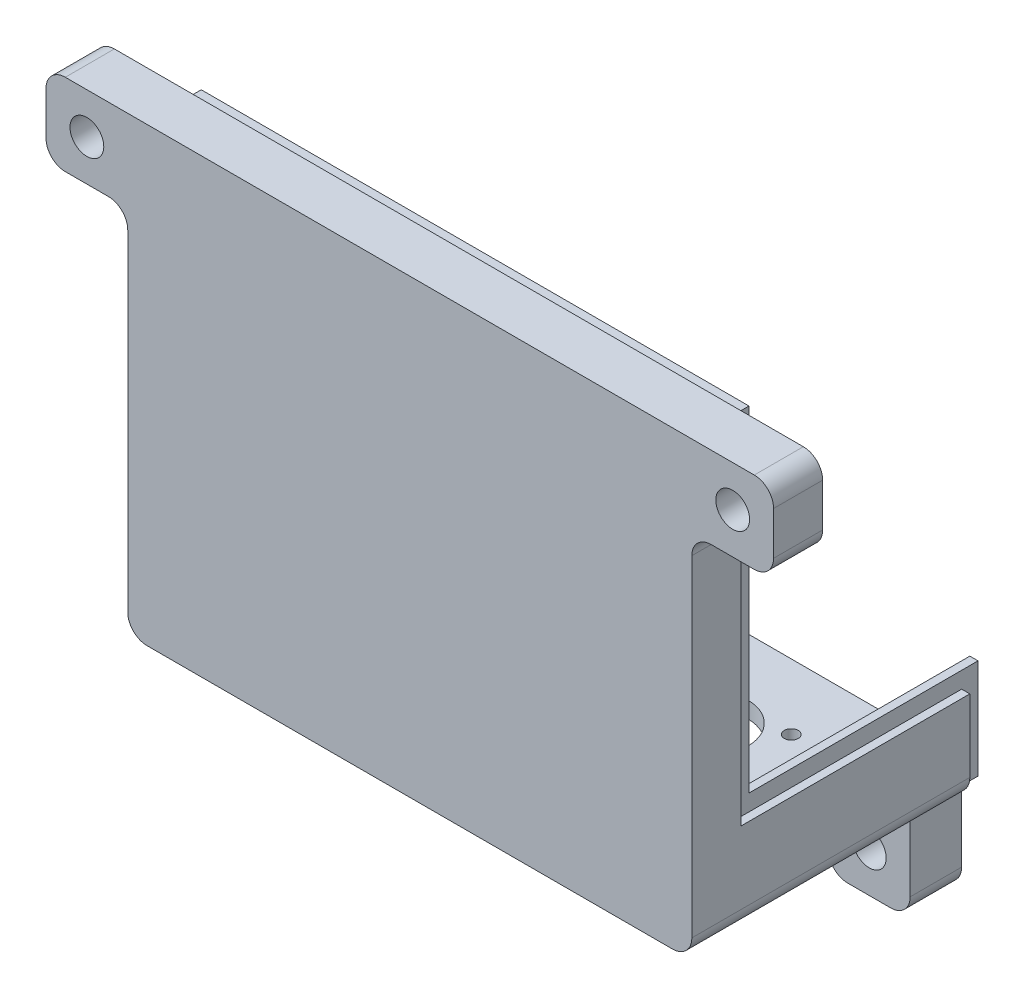
SolidWorks part; units mm, degrees
material "ABS"
ref_plane "X-Y Datum" through (0, 0, 0) normal (0, 0, 1) x (1, 0, 0)
ref_plane "X-Z Datum" through (0, 0, 0) normal (0, 1, 0) x (1, 0, 0)
ref_plane "Y-Z Datum" through (0, 0, 0) normal (1, 0, 0) x (0, 0, -1)
sketch "Sketch1" plane through (0, 0, 0) normal (0, 0, 1) x (1, 0, 0)
  line L0 (6.33, 73.27) -> (88.87, 73.27)
  line L1 (7.6, 72) -> (87.6, 72) construction
  line L2 (7.6, 72) -> (7.6, 9.5) construction
  line L3 (7.6, 9.5) -> (87.6, 9.5) construction
  line L4 (87.6, 72) -> (87.6, 9.5) construction
  line L5 (88.87, 73.27) -> (88.87, 8.23)
  line L6 (6.33, 8.23) -> (88.87, 8.23)
  line L7 (6.33, 73.27) -> (6.33, 8.23)
  circle A0 centre (12.6, 67) radius 2.125 construction
  circle A1 centre (82.6, 67) radius 2.125 construction
  circle A2 centre (82.6, 17) radius 2.125 construction
  circle A3 centre (12.6, 17) radius 2.125 construction
  dimension "D1" = 1.27
extrude "Boss-Extrude1" add sketch "Sketch1" along normal blind 43.18
shell "Shell1" thickness 2.54
sketch "Sketch2" plane through (97.1, 5.69, 0) normal (0, 1, 0) x (0, 0, -1)
  line L0 (-9.166, 49.5) -> (-32.766, 49.5) construction
  line L1 (-32.766, 71.1371) -> (-32.766, 27.8629) construction
  line L2 (-32.766, 71.1371) -> (-9.166, 71.1371) construction
  line L3 (-9.166, 71.1371) -> (-9.166, 54.9902) construction
  line L4 (-32.766, 27.8629) -> (-9.166, 27.8629) construction
  line L5 (-32.766, 71.1371) -> (-9.166, 27.8629) construction
  line L6 (-9.166, 71.1371) -> (-32.766, 27.8629) construction
  line L8 (-9.166, 54.9902) -> (-7.166, 54.9902) construction
  line L9 (-7.166, 54.9902) -> (-7.166, 44.0098) construction
  line L10 (-9.166, 44.0098) -> (-7.166, 44.0098) construction
  line L11 (-9.166, 49.5) -> (-7.166, 44.0098) construction
  line L12 (-7.166, 54.9902) -> (-9.166, 49.5) construction
  line L13 (-43.18, 49.5) -> (-33.02, 49.5) construction
  line L14 (-43.18, 90.77) -> (-43.18, 8.23) construction
  line L16 (-9.166, 44.0098) -> (-9.166, 27.8629) construction
  line L17 (-33.02, 71.3911) -> (-8.912, 71.3911)
  line L18 (-8.912, 71.3911) -> (-8.912, 55.2442)
  line L19 (-8.912, 55.2442) -> (-6.912, 55.2442)
  line L20 (-6.912, 55.2442) -> (-6.912, 43.7558)
  line L21 (-8.912, 43.7558) -> (-6.912, 43.7558)
  line L22 (-8.912, 43.7558) -> (-8.912, 27.6089)
  line L23 (-33.02, 27.6089) -> (-8.912, 27.6089)
  line L24 (-33.02, 71.3911) -> (-33.02, 27.6089)
  circle A0 centre (-10.166, 73.2) radius 1.085
  circle A1 centre (-10.166, 25.8) radius 1.085
  circle A2 centre (-28.266, 24.3) radius 1.085
  circle A3 centre (-28.266, 74.7) radius 1.085
  point P10 (-20.966, 49.5)
  point P25 (-20.966, 49.5)
  point P34 (-20.966, 49.5)
  dimension "D1" = 0.254
extrude "Cut-Extrude1" cut sketch "Sketch2" along normal through all
fillet "Fillet1" radius 6.2001 4 edges at (25.7089, 6.96, 33.02) (69.4911, 6.96, 33.02) (69.4911, 6.96, 8.912) (25.7089, 6.96, 8.912)
fillet "Fillet2" radius 1 4 edges at (53.3442, 6.96, 8.912) (53.3442, 6.96, 6.912) (41.8558, 6.96, 8.912) (41.8558, 6.96, 6.912)
sketch "Sketch6" plane through (3.79, 0, 0) normal (-1, 0, 0) x (0, 0, 1)
  line L5 (0, 73.27) -> (35.56, 73.27)
  line L6 (0, 73.27) -> (0, 22.47)
  line L7 (0, 22.47) -> (35.56, 22.47)
  line L8 (35.56, 73.27) -> (35.56, 22.47)
extrude "Cut-Extrude2" cut sketch "Sketch6" against normal through all
sketch "Sketch3" plane through (0, 0, 43.18) normal (0, 0, -1) x (-1, 0, 0)
  line L0 (-86.5144, 72) -> (-78.6856, 72)
  line L1 (-7.6, 70.9144) -> (-7.6, 63.0856)
  line L3 (-86.5144, 72) -> (-78.6856, 72) construction
  line L4 (-87.6, 70.9144) -> (-87.6, 63.0856) construction
  line L5 (-87.6, 9.5) -> (-7.6, 9.5) construction
  line L6 (-7.6, 70.9144) -> (-7.6, 63.0856) construction
  line L7 (-8.6856, 72) -> (-16.5144, 72)
  line L8 (-7.6, 20.9144) -> (-7.6, 13.0856)
  line L9 (-87.6, 20.9144) -> (-87.6, 13.0856)
  line L10 (-87.6, 20.9144) -> (-87.6, 13.0856) construction
  line L11 (-16.5144, 72) -> (-8.6856, 72) construction
  line L12 (-7.6, 20.9144) -> (-7.6, 13.0856) construction
  line L13 (-87.6, 70.9144) -> (-87.6, 63.0856)
  circle A0 centre (-82.6, 67) radius 2.125
  circle A1 centre (-12.6, 67) radius 2.125
  circle A2 centre (-12.6, 17) radius 2.125
  circle A3 centre (-82.6, 17) radius 2.125
  arc A4 (-87.6, 63.0856) -> (-78.6856, 72) centre (-82.6, 67) ccw
  arc A5 (-16.5144, 72) -> (-7.6, 63.0856) centre (-12.6, 67) ccw
  arc A6 (-87.6, 13.0856) -> (-87.6, 20.9144) centre (-82.6, 17) ccw
  arc A7 (-7.6, 20.9144) -> (-7.6, 13.0856) centre (-12.6, 17) ccw
  arc A8 (-86.5144, 72) -> (-87.6, 70.9144) centre (-82.6, 67) ccw
  arc A9 (-7.6, 70.9144) -> (-8.6856, 72) centre (-12.6, 67) ccw
  point P18 (-47.6, 40.75)
extrude "Boss-Extrude2" add sketch "Sketch3" along normal blind 9.3904
sketch "Sketch7" plane through (0, 0, 0) normal (0, 0, -1) x (-1, 0, 0)
  line L0 (-91.41, 22.47) -> (-90.14, 22.47)
  line L1 (-91.41, 22.47) -> (-88.87, 22.47) construction
  line L2 (-88.87, 8.23) -> (-88.87, 5.69) construction
  line L3 (-3.79, 5.69) -> (-91.41, 5.69) construction
  line L4 (-90.14, 22.47) -> (-90.14, 6.96)
  line L5 (-90.14, 6.96) -> (-5.06, 6.96)
  line L6 (-5.06, 6.96) -> (-5.06, 22.47)
  line L7 (-6.33, 22.47) -> (-3.79, 22.47) construction
  line L8 (-5.06, 22.47) -> (-3.79, 22.47)
  line L9 (-3.79, 22.47) -> (-3.79, 5.69)
  line L10 (-3.79, 5.69) -> (-91.41, 5.69)
  line L11 (-91.41, 5.69) -> (-91.41, 22.47)
extrude "Cut-Extrude3" cut sketch "Sketch7" against normal blind 2.54
sketch "Sketch8" plane through (0, 22.47, 0) normal (0, 1, 0) x (1, 0, 0)
  line L0 (5.06, -2.54) -> (5.06, -35.56)
  line L1 (6.33, -35.56) -> (3.79, -35.56) construction
  line L2 (5.06, -35.56) -> (3.79, -35.56)
  line L3 (3.79, -35.56) -> (3.79, -2.54)
  line L4 (3.79, -2.54) -> (5.06, -2.54)
  line L5 (90.14, -2.54) -> (90.14, -35.56)
  line L6 (91.41, -35.56) -> (88.87, -35.56) construction
  line L7 (90.14, -35.56) -> (91.41, -35.56)
  line L8 (91.41, -35.56) -> (91.41, -2.54)
  line L9 (91.41, -2.54) -> (90.14, -2.54)
extrude "Cut-Extrude4" cut sketch "Sketch8" against normal blind 2.54
sketch "Sketch10" plane through (0, 73.27, 0) normal (0, 1, 0) x (1, 0, 0)
  line L0 (3.79, -2.54) -> (3.79, -35.56) construction
  line L1 (3.79, -35.5747) -> (91.41, -35.5747)
  line L2 (3.79, -35.5747) -> (3.79, -45.72)
  line L3 (3.79, -45.72) -> (91.41, -45.72)
  line L4 (91.41, -35.5747) -> (91.41, -45.72)
extrude "Boss-Extrude3" add sketch "Sketch10" along normal blind 2.54
sketch "Sketch9" plane through (0, 0, 35.56) normal (0, 0, -1) x (-1, 0, 0)
  line L0 (-90.14, 73.27) -> (-90.14, 74.54)
  line L1 (-90.14, 19.93) -> (-91.41, 19.93)
  line L2 (-90.14, 19.93) -> (-90.14, 73.27)
  line L4 (-91.41, 19.93) -> (-91.41, 73.27)
  line L5 (-5.06, 19.93) -> (-3.79, 19.93)
  line L6 (-5.06, 19.93) -> (-5.06, 73.27)
  line L8 (-3.79, 19.93) -> (-3.79, 73.27)
  line L9 (-90.14, 74.54) -> (-5.06, 74.54)
  line L10 (-5.06, 74.54) -> (-5.06, 73.27)
  line L11 (-3.79, 73.27) -> (-3.79, 75.81)
  line L12 (-3.79, 75.81) -> (-91.41, 75.81)
  line L13 (-91.41, 75.81) -> (-91.41, 73.27)
extrude "Cut-Extrude5" cut sketch "Sketch9" against normal blind 2.54
sketch "Sketch11" plane through (0, 5.69, 0) normal (0, -1, 0) x (1, 0, 0)
  line L0 (47.6, 45.72) -> (47.6, -4.8901) construction
  line L5 (3.79, 45.72) -> (91.41, 45.72) construction
  line L6 (90.14, 10.54) -> (77.44, 10.54)
  line L7 (77.44, 2.54) -> (77.44, 10.54)
  line L8 (90.14, 2.54) -> (77.44, 2.54)
  line L9 (90.14, 2.54) -> (90.14, 10.54)
  line L10 (5.06, 2.54) -> (5.06, 10.54)
  line L11 (5.06, 2.54) -> (17.76, 2.54)
  line L12 (17.76, 2.54) -> (17.76, 10.54)
  line L13 (5.06, 10.54) -> (17.76, 10.54)
extrude "Boss-Extrude4" add sketch "Sketch11" along normal blind 12.7
sketch "Sketch12" plane through (0, 0, 2.54) normal (0, 0, -1) x (-1, 0, 0)
  line L0 (-90.14, 5.69) -> (-77.44, 5.69) construction
  line L1 (-83.79, 5.69) -> (-83.79, -7.01) construction
  line L2 (-77.44, -7.01) -> (-90.14, -7.01) construction
  line L3 (-17.76, 5.69) -> (-5.06, 5.69) construction
  line L4 (-11.41, 5.69) -> (-11.41, -7.01) construction
  line L5 (-5.06, -7.01) -> (-17.76, -7.01) construction
  circle A0 centre (-83.79, -0.66) radius 2.625
  circle A1 centre (-11.41, -0.66) radius 2.625
  point P16 (-83.79, -0.66)
  point P17 (-11.41, -0.66)
extrude "Cut-Extrude6" cut sketch "Sketch12" against normal through all
sketch "Sketch13" plane through (3.79, 0, 0) normal (-1, 0, 0) x (0, 0, 1)
  line L0 (45.72, 75.81) -> (45.72, 5.69) construction
  line L1 (38.1, 75.81) -> (45.72, 75.81)
  line L2 (38.1, 75.81) -> (38.1, 63.11)
  line L3 (38.1, 63.11) -> (45.72, 63.11)
  line L4 (45.72, 75.81) -> (45.72, 63.11)
extrude "Boss-Extrude5" add sketch "Sketch13" along normal blind 12.7
sketch "Sketch14" plane through (0, 0, 38.1) normal (0, 0, -1) x (-1, 0, 0)
  line L0 (2.56, 63.11) -> (2.56, 75.81) construction
  line L1 (8.91, 63.11) -> (-3.79, 63.11) construction
  line L2 (8.91, 75.81) -> (-91.41, 75.81) construction
  circle A0 centre (2.56, 69.46) radius 2.625
extrude "Cut-Extrude7" cut sketch "Sketch14" against normal through all
ref_plane "Plane1" through (47.6, 0, 0) normal (-1, 0, 0) x (0, 0, 1)
mirror "Mirror1" about plane through (47.6, 0, 0) normal (-1, 0, 0) of "Boss-Extrude5", "Cut-Extrude7"
sketch "Sketch15" plane through (0, 0, 45.72) normal (0, 0, 1) x (1, 0, 0)
  line L1 (5.06, 5.69) -> (17.76, 5.69)
  line L2 (5.06, 5.69) -> (5.06, -7.01)
  line L3 (5.06, -7.01) -> (17.76, -7.01)
  line L4 (17.76, 5.69) -> (17.76, -7.01)
  line L5 (77.44, 5.69) -> (90.14, 5.69)
  line L6 (77.44, 5.69) -> (77.44, -7.01)
  line L7 (77.44, -7.01) -> (90.14, -7.01)
  line L8 (90.14, 5.69) -> (90.14, -7.01)
  line L9 (3.79, 63.11) -> (-8.91, 63.11)
  line L10 (3.79, 63.11) -> (3.79, 50.41)
  line L11 (3.79, 50.41) -> (-8.91, 50.41)
  line L12 (-8.91, 63.11) -> (-8.91, 50.41)
  line L13 (91.41, 63.11) -> (104.11, 63.11)
  line L14 (91.41, 63.11) -> (91.41, 50.41)
  line L15 (91.41, 50.41) -> (104.11, 50.41)
  line L16 (104.11, 63.11) -> (104.11, 50.41)
  circle A0 centre (11.41, -0.66) radius 2.508
  circle A1 centre (83.79, -0.66) radius 2.508
  circle A2 centre (-2.56, 56.76) radius 2.508
  circle A3 centre (97.76, 56.76) radius 2.508
extrude "Boss-Extrude6" [suppressed] add sketch "Sketch15" against normal blind 2.54
fillet "Fillet3" radius 3 20 edges at (6.33, 73.27, 39.3774) (6.33, 8.23, 21.59) (88.87, 8.23, 21.59) (88.87, 73.27, 39.3774) (17.76, 5.69, 6.54) (5.06, 5.69, 6.54) (17.76, -7.01, 6.54) (5.06, -7.01, 6.54) (90.14, 5.69, 6.54) (77.44, 5.69, 6.54) (90.14, -7.01, 6.54) (77.44, -7.01, 6.54) (3.79, 63.11, 41.91) (-8.91, 63.11, 41.91) (-8.91, 75.81, 41.91) (104.11, 75.81, 41.91) (104.11, 63.11, 41.91) (91.41, 63.11, 41.91) (91.41, 5.69, 24.13) (3.79, 5.69, 24.13)
